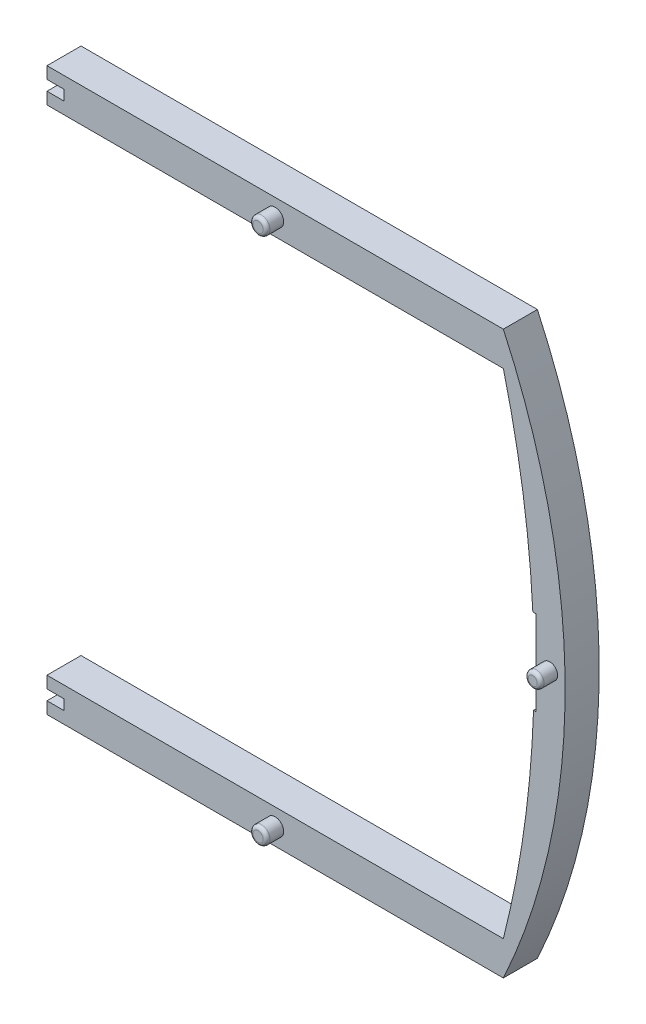
SolidWorks part; units mm, degrees
ref_plane "Plan de face" through (0, 0, 0) normal (0, 0, 1) x (1, 0, 0)
ref_plane "Plan de dessus" through (0, 0, 0) normal (0, 1, 0) x (1, 0, 0)
ref_plane "Plan de droite" through (0, 0, 0) normal (1, 0, 0) x (0, 0, -1)
sketch "Esquisse1" plane through (0, 0, 0) normal (0, 0, 1) x (1, 0, 0)
  line L0 (-18.7878, -102.4749) -> (-18.776, -105.9749)
  line L1 (-18.776, 42.5251) -> (115.224, 42.5251)
  line L2 (-18.776, 42.5251) -> (-18.7878, -102.4749)
  line L3 (-18.7878, -102.4749) -> (115.224, -102.4749)
  line L4 (115.224, 42.5251) -> (115.224, -102.4749)
  line L5 (115.224, 42.5251) -> (-18.776, 42.5251)
  line L6 (115.224, 42.5251) -> (115.224, 52.5251)
  line L7 (115.224, 52.5251) -> (-18.776, 52.5251)
  line L8 (-18.776, 42.5251) -> (-18.776, 52.5251)
  line L9 (115.224, -102.4749) -> (-18.7878, -102.4749)
  line L10 (115.224, -102.4749) -> (115.224, -112.4749)
  line L11 (115.224, -112.4749) -> (-18.7878, -112.4749)
  line L12 (-18.776, -108.9749) -> (-18.7878, -112.4749)
  line L13 (-18.776, -105.9749) -> (-13.776, -105.9749)
  line L15 (-18.776, 49.0251) -> (-13.776, 49.0251)
  line L16 (-18.776, -108.9749) -> (-13.776, -108.9749)
  line L17 (-13.7878, -112.4749) -> (-18.7878, -112.4749)
  line L18 (-13.776, -105.9749) -> (-13.776, -108.9749)
  line L19 (-18.776, 49.0251) -> (-18.776, 46.0251)
  line L20 (124.7917, -15.0592) -> (121.7917, -15.0592)
  line L21 (124.7917, -15.0592) -> (124.7917, -39.9749)
  line L22 (124.7917, -39.9749) -> (121.7917, -39.9749)
  line L23 (121.7917, -15.0592) -> (121.7917, -39.9749)
  line L24 (-18.776, 46.0251) -> (-13.776, 46.0251)
  line L25 (-14.1239, 42.5251) -> (-18.776, 42.5251)
  line L26 (-13.776, 49.0251) -> (-13.776, 46.0251)
  line L28 (-18.776, 42.5251) -> (-18.776, 47.7687)
  line L31 (-14.1239, 52.5251) -> (-18.776, 52.5251)
  line L32 (-18.776, 51.0096) -> (-18.776, 52.5251)
  arc A0 (115.224, -102.4749) -> (115.224, 42.5251) centre (-171.1264, -29.9749) ccw
  arc A1 (115.224, 52.5251) -> (115.224, -112.4749) centre (-63.2148, -29.9749) cw
  circle A2 centre (128.8639, -27.5592) radius 2.3137
  circle A4 centre (48.224, -107.4749) radius 2.5
  circle A5 centre (48.224, 47.5251) radius 2.5
  dimension "D10" = 12.5
  dimension "D5" = 300
  dimension "D8" = 145
  dimension "D1" = 134
  dimension "D3" = 67
  dimension "D4" = 67
  dimension "D6" = 10
  dimension "D7" = 5
  dimension "D9" = 3
  dimension "D13" = 3
  dimension "D14" = 3.5
  dimension "D15" = 5
  dimension "D16" = 3.5
  dimension "D17" = 3
  dimension "D18" = 10
  dimension "D21" = 5
  dimension "D22" = 5
extrude "Boss.-Extru.9" add sketch "Esquisse1" along normal blind 10 contours L15 L26 L24 L8 L1 L5 L6 L7 A5 | A1 L6 A0 L20 L21 L22 L10 A2 | L13 L18 L16 L12 L11 L10 L3 L0 A4 region at (48.2181, -103.8187, 0) region at (-17.4323, 44.2751, 0) region at (125.2937, -30.0561, 0)
extrude "Boss.-Extru.10" add sketch "Esquisse1<31>" along normal blind 2 contours L23 L22 L21 L20
sketch "Esquisse1<31>" plane through (0, 0, 0) normal (0, 0, 1) x (1, 0, 0) same geometry as "Esquisse1"
extrude "Boss.-Extru.11" add sketch "Esquisse1<32>" along normal blind 15 contours A5 | A2 | A4 region at (128.8639, -27.5592, 0) region at (48.224, -107.4749, 0) region at (48.224, 47.5251, 0)
sketch "Esquisse1<32>" plane through (0, 0, 0) normal (0, 0, 1) x (1, 0, 0) same geometry as "Esquisse1"
fillet "Congé1" radius 1 3 edges at (50.724, 47.5251, 15) (131.1776, -27.5592, 15) (50.724, -107.4749, 15)
fillet "Congé2" radius 0.5 2 edges at (121.7917, -27.517, 0) (121.7917, -27.517, 2)
